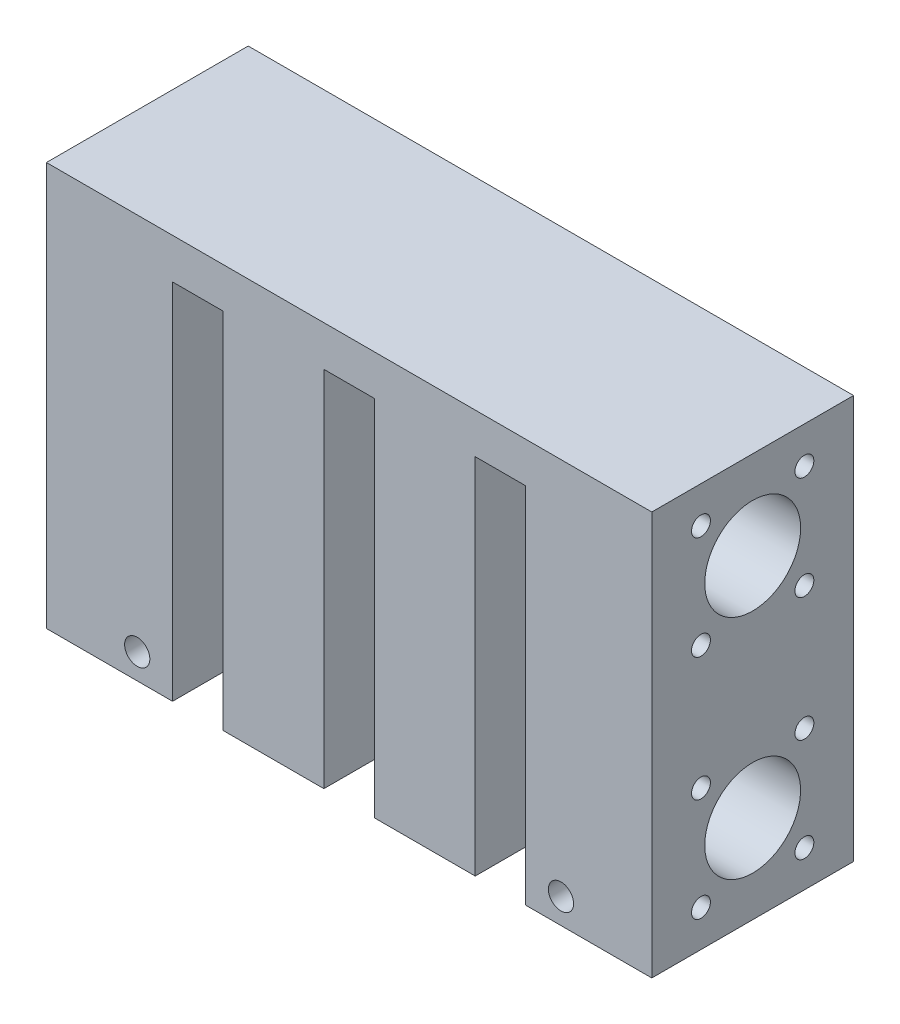
SolidWorks part; units mm, degrees
material "1060 Alloy"
ref_plane "Front Plane" through (0, 0, 0) normal (0, 0, 1) x (1, 0, 0)
ref_plane "Top Plane" through (0, 0, 0) normal (0, 1, 0) x (1, 0, 0)
ref_plane "Right Plane" through (0, 0, 0) normal (1, 0, 0) x (0, 0, -1)
sketch "Sketch1" plane through (0, 0, 0) normal (0, 0, 1) x (1, 0, 0)
  line L1 (0, 0) -> (120, 0)
  line L2 (0, 0) -> (0, 80)
  line L3 (0, 80) -> (120, 80)
  line L4 (120, 0) -> (120, 80)
  dimension "D1" = 80
  dimension "D2" = 120
extrude "Boss-Extrude1" add sketch "Sketch1" along normal blind 40 contours L3 L4 L1 L2
sketch "Sketch2" plane through (0, 0, 0) normal (-1, 0, 0) x (0, 0, 1)
  line L0 (20, 80) -> (20, 0) construction
  line L1 (40, 80) -> (0, 80) construction
  line L2 (40, 0) -> (0, 0) construction
  line L3 (40, 40) -> (0, 40) construction
  line L4 (40, 0) -> (40, 80) construction
  line L5 (0, 0) -> (0, 80) construction
  line L6 (0, 62.5) -> (40, 62.5) construction
  line L7 (0, 17.5) -> (40, 17.5) construction
  circle A1 centre (30.25, 72.75) radius 1.85
  circle A2 centre (9.75, 72.75) radius 1.85
  circle A3 centre (30.25, 52.25) radius 1.85
  circle A4 centre (9.75, 52.25) radius 1.85
  circle A5 centre (9.75, 27.75) radius 1.85
  circle A6 centre (30.25, 27.75) radius 1.85
  circle A7 centre (30.25, 7.25) radius 1.85
  circle A9 centre (9.75, 7.25) radius 1.85
  dimension "D4" = 3.7
  dimension "D1" = 22.5
  dimension "D2" = 9.75
  dimension "D3" = 7.25
extrude "linear-bearing-screw-cuts" cut sketch "Sketch2" against normal blind 14
sketch "Sketch3" plane through (0, 0, 0) normal (-1, 0, 0) x (0, 0, 1)
  line L0 (20, 80) -> (20, 0) construction
  line L1 (40, 80) -> (0, 80) construction
  line L2 (40, 0) -> (0, 0) construction
  line L3 (0, 40) -> (40, 40) construction
  line L4 (0, 0) -> (0, 80) construction
  line L5 (40, 0) -> (40, 80) construction
  line L6 (0, 62.5) -> (40, 62.5) construction
  line L7 (0, 17.5) -> (40, 17.5) construction
  circle A0 centre (20, 62.5) radius 9.5
  circle A2 centre (20, 17.5) radius 9.5
  dimension "D2" = 19
  dimension "D1" = 45
extrude "linear-bearings-hole" cut sketch "Sketch3" against normal blind 55
sketch "Sketch4" plane through (120, 0, 0) normal (1, 0, 0) x (0, 0, -1)
  line L0 (-20, 80) -> (-20, 0) construction
  line L1 (-40, 80) -> (0, 80) construction
  line L2 (-40, 0) -> (0, 0) construction
  line L3 (-40, 40) -> (0, 40) construction
  line L4 (-40, 0) -> (-40, 80) construction
  line L5 (0, 0) -> (0, 80) construction
  line L6 (-40, 62.5) -> (0, 62.5) construction
  line L7 (-40, 17.5) -> (0, 17.5) construction
  circle A0 centre (-9.75, 72.75) radius 1.875
  circle A1 centre (-30.25, 72.75) radius 1.875
  circle A2 centre (-9.75, 52.25) radius 1.875
  circle A3 centre (-30.25, 52.25) radius 1.875
  circle A4 centre (-30.25, 27.75) radius 1.875
  circle A5 centre (-9.75, 27.75) radius 1.875
  circle A6 centre (-9.75, 7.25) radius 1.875
  circle A7 centre (-30.25, 7.25) radius 1.875
  dimension "D2" = 3.75
  dimension "D1" = 45
  dimension "D3" = 7.25
  dimension "D4" = 9.75
extrude "linear-bearing-screw-cuts2" cut sketch "Sketch4" against normal blind 14
sketch "Sketch5" plane through (120, 0, 0) normal (1, 0, 0) x (0, 0, -1)
  line L0 (-20, 80) -> (-20, 0) construction
  line L1 (-40, 80) -> (0, 80) construction
  line L2 (-40, 0) -> (0, 0) construction
  line L3 (0, 40) -> (-40, 40) construction
  line L4 (0, 0) -> (0, 80) construction
  line L5 (-40, 0) -> (-40, 80) construction
  line L6 (-40, 62.5) -> (0, 62.5) construction
  line L7 (-40, 17.5) -> (0, 17.5) construction
  circle A0 centre (-20, 62.5) radius 9.5
  circle A1 centre (-20, 17.5) radius 9.5
  dimension "D2" = 19
  dimension "D1" = 45
extrude "Cut-Extrude4" cut sketch "Sketch5" against normal blind 55
sketch "Sketch10" plane through (0, 0, 0) normal (0, -1, 0) x (1, 0, 0)
  line L0 (85, 40) -> (85, 30)
  line L1 (0, 40) -> (120, 40) construction
  line L2 (85, 30) -> (95, 30)
  line L3 (95, 30) -> (95, 40)
  line L4 (95, 40) -> (85, 40)
  line L5 (60, 40) -> (60, 0) construction
  line L6 (0, 0) -> (120, 0) construction
  line L7 (75, 40) -> (75, 0) construction
  line L8 (120, 40) -> (120, 0) construction
  line L9 (55, 30) -> (55, 40)
  line L10 (65, 30) -> (55, 30)
  line L11 (65, 40) -> (65, 30)
  line L12 (55, 40) -> (65, 40)
  line L13 (25, 30) -> (25, 40)
  line L14 (35, 30) -> (25, 30)
  line L15 (35, 40) -> (35, 30)
  line L16 (25, 40) -> (35, 40)
  point P12 (90, 40)
  dimension "D1" = 30
  dimension "D2" = 10
  dimension "D3" = 10
  dimension "D4" = 10
  dimension "D6" = 45
extrude "Cut-Extrude8" cut sketch "Sketch10" against normal blind 72
sketch "Sketch11" plane through (65, 0, 0) normal (1, 0, 0) x (0, 0, -1)
  circle A0 centre (-20, 62.5) radius 6
  circle A1 centre (-20, 17.5) radius 6
  dimension "D1" = 12
extrude "Cut-Extrude9" cut sketch "Sketch11" against normal through all
sketch "Sketch12" plane through (0, 0, 40) normal (0, 0, 1) x (1, 0, 0)
  line L0 (120, 0) -> (120, 80) construction
  line L1 (0, 0) -> (0, 80) construction
  line L2 (0, 80) -> (120, 80) construction
  circle A0 centre (5.5, 74.5) radius 1.25
  circle A1 centre (36.5, 74.5) radius 1.25
  circle A2 centre (83.5, 74.5) radius 1.25
  circle A3 centre (114.5, 74.5) radius 1.25
  circle A4 centre (5.5, 43.5) radius 1.25
  circle A5 centre (36.5, 43.5) radius 1.25
  circle A6 centre (83.5, 43.5) radius 1.25
  circle A7 centre (114.5, 43.5) radius 1.25
  dimension "D4" = 2.5
  dimension "D1" = 31
  dimension "D2" = 31
  dimension "D3" = 31
  dimension "D5" = 5.5
  dimension "D6" = 5.5
  dimension "D7" = 5.5
extrude "Cut-Extrude10" [suppressed] cut sketch "Sketch12" against normal through all
sketch "Sketch13" plane through (0, 0, 0) normal (0, 0, -1) x (-1, 0, 0)
  line L1 (-120, 0) -> (-120, 80) construction
  line L2 (0, 0) -> (0, 80) construction
  line L3 (0, 0) -> (-120, 0) construction
  circle A0 centre (-102, 5) radius 2.5
  circle A1 centre (-18, 5) radius 2.5
  point P4 (0, 0)
  dimension "D3" = 5
  dimension "D4" = 18
  dimension "D1" = 5
  dimension "D2" = 18
extrude "Cut-Extrude11" cut sketch "Sketch13" against normal through all
